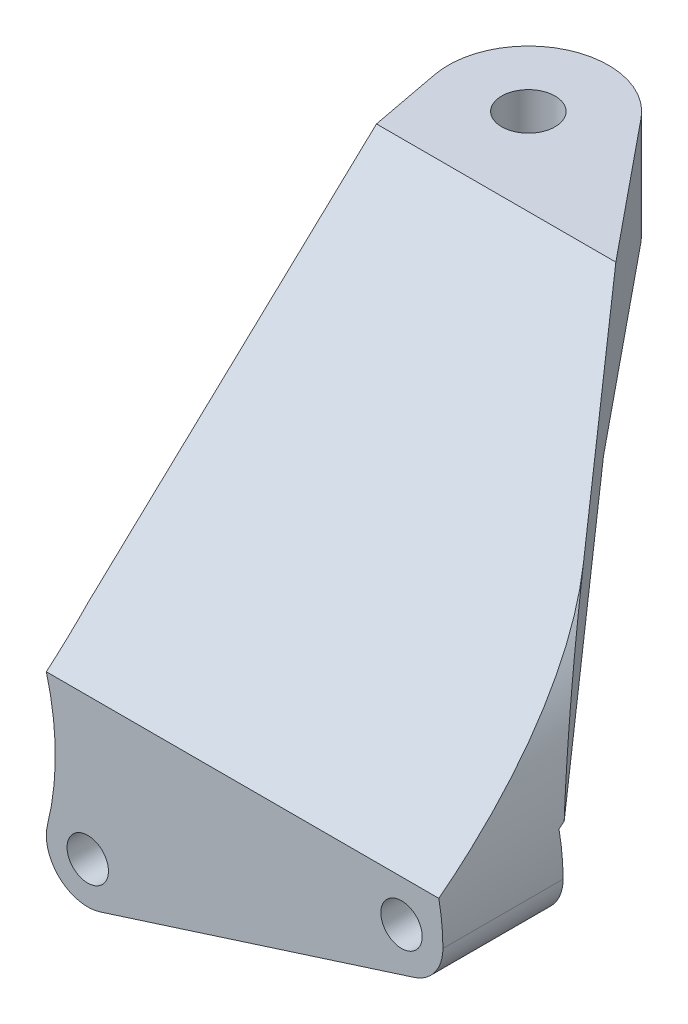
SolidWorks part; units mm, degrees
material "6061 Alloy"
ref_plane "Front Plane" through (0, 0, 0) normal (0, 0, 1) x (1, 0, 0)
ref_plane "Top Plane" through (0, 0, 0) normal (0, 1, 0) x (1, 0, 0)
ref_plane "Right Plane" through (0, 0, 0) normal (1, 0, 0) x (0, 0, -1)
sketch "Sketch1" plane through (0, 0, 0) normal (0, 0, 1) x (1, 0, 0)
  line L0 (26.6, 7.5073) -> (26.6, 10.6073)
  line L1 (0, 0) -> (23.5, 7.5073) construction
  line L6 (23.5, 7.5073) -> (0, 7.5073) construction
  line L7 (0, -55) -> (0, 55) construction
  line L8 (-3.1, 10.6073) -> (26.6, 10.6073)
  line L10 (0, 7.5073) -> (0, 0) construction
  line L11 (-3.1, 10.6073) -> (-3.1, 0)
  line L13 (24.4434, 4.5543) -> (0.9434, -2.953)
  circle A0 centre (0, 0) radius 1.55
  circle A2 centre (23.5, 7.5073) radius 1.55
  arc A3 (24.4434, 4.5543) -> (26.6, 7.5073) centre (23.5, 7.5073) ccw
  arc A4 (-3.1, 0) -> (0.9434, -2.953) centre (0, 0) ccw
  dimension "D2" = 3.1
  dimension "D3" = 6.2
  dimension "D1" = 24.67
  dimension "D4" = 3.1
  dimension "D6" = 23.5
extrude "Boss-Extrude1" add sketch "Sketch1" against normal blind 9
ref_plane "Plane1" through (0, 28, 0) normal (0, 1, 0) x (1, 0, 0)
sketch "Sketch7" plane through (0, 28, 0) normal (0, 1, 0) x (1, 0, 0)
  line L0 (0, -4.95) -> (0, 4.95) construction
  line L1 (-7.539, 0) -> (7.539, 0) construction
  line L3 (-3.1, 0) -> (-9.8952, 35.8836)
  line L4 (-3.1, 0) -> (26.6, 0)
  line L5 (26.6, 9) -> (0.6481, 40.794)
  line L6 (26.6, 9) -> (26.6, 0)
  circle A0 centre (-4, 37) radius 2
  arc A1 (0.6481, 40.794) -> (-9.8952, 35.8836) centre (-4, 37) ccw
  point P7 (-3.1, 0)
  point P8 (26.6, 0)
  dimension "D1" = 4
  dimension "D3" = 12
  dimension "D2" = 4
  dimension "D4" = 37
extrude "Boss-Extrude12" add sketch "Sketch7" against normal up to surface (17.3927 mm away) contours L3 A1 L5 L6 L4 up to face at (11.75, 10.6073, -4.5)
extrude "Cut-Extrude3" cut sketch "Sketch7<3>" against normal up to surface (17.3927 mm away) flip side to cut up to face at (1.8487, 10.6073, -19.7556)
sketch "Sketch7<3>" plane through (0, 28, 0) normal (0, 1, 0) x (1, 0, 0) same geometry as "Sketch7"
sketch "Sketch8" plane through (0, 0, 0) normal (1, 0, 0) x (0, 0, -1)
  line L0 (0, 10.6073) -> (30.5, 28)
  line L1 (0, 17.105) -> (0, -17.105) construction
  line L3 (13.6887, 28) -> (-13.6887, 28) construction
  line L4 (30.5, 28) -> (0, 28)
  line L5 (0, 28) -> (0, 10.6073)
  line L6 (37, 10.6073) -> (37, 28) construction
  line L7 (43, 20) -> (25.4712, 20)
  line L8 (43, 10.6073) -> (43, 28) construction
  line L9 (43, 20) -> (43, 10.6073)
  line L10 (43, 10.6073) -> (9, 10.6073)
  line L11 (9, 10.6073) -> (25.4712, 20)
  line L12 (9, 10.6073) -> (0, 10.6073) construction
  dimension "D1" = 6.5
  dimension "D2" = 8
  dimension "D3" = 4.4583
extrude "Cut-Extrude2" cut sketch "Sketch8" against normal mid plane 100
sketch "Sketch12" plane through (0, 0, 0) normal (0, 0, 1) x (1, 0, 0)
  line L1 (-7.9234, 20) -> (-4.8043, 10.6073) construction
  line L2 (20.13, 0) -> (-20.13, 0) construction
  line L3 (-10, 28) -> (-10, 20) construction
  line L4 (-3.1, 0) -> (-7.4936, 18.7056)
  arc A2 (-3.0088, 0.7463) -> (-3.1, 0) centre (0, 0) ccw
  arc A3 (-7.4936, 18.7056) -> (-3.0088, 0.7463) centre (-22.174, 5.5) cw
  dimension "D3" = 19.7459
  dimension "D2" = 12.174
  dimension "D1" = 5.5
extrude "Cut-Extrude5" cut sketch "Sketch12" against normal through all
sketch "Sketch14" plane through (0, 0, 0) normal (0, 0, 1) x (1, 0, 0)
  line L0 (26.6, 15.7395) -> (9.0506, 28) construction
  line L1 (19.8515, 20.4542) -> (26.6, 15.7395)
  line L2 (26.6, 15.7395) -> (26.6, 7.5073)
  arc A0 (26.6, 7.5073) -> (19.8515, 20.4542) centre (10.8064, 7.5073) ccw
extrude "Cut-Extrude7" cut sketch "Sketch14" against normal through all
